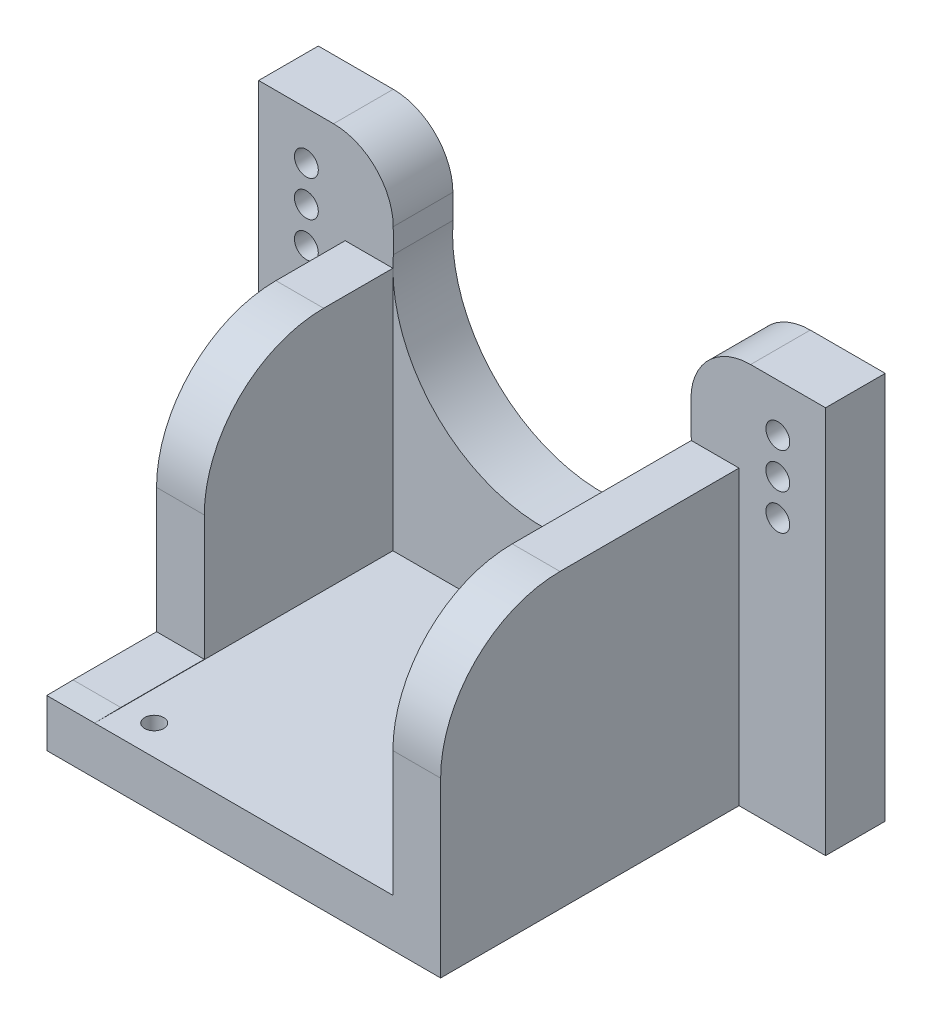
SolidWorks part; units mm, degrees
ref_plane "Front Plane" through (0, 0, 0) normal (0, 0, 1) x (1, 0, 0)
ref_plane "Top Plane" through (0, 0, 0) normal (0, 1, 0) x (1, 0, 0)
ref_plane "Right Plane" through (0, 0, 0) normal (1, 0, 0) x (0, 0, -1)
sketch "Sketch1" plane through (0, 0, 0) normal (0, 0, 1) x (1, 0, 0)
  line L0 (-25, 20.9224) -> (-66.8811, 20.9224) construction
  line L1 (-25, 12.9224) -> (-25, -3.0776) construction
  line L2 (25, 12.9224) -> (25, -3.0776) construction
  line L3 (-25, 4.9224) -> (25, 4.9224) construction
  line L4 (61.331, -36.0776) -> (47.5, -36.0776) construction
  line L5 (-39.5, 14.9224) -> (-39.5, -45.2177) construction
  line L6 (39.5, 12.9224) -> (39.5, -45.2177) construction
  line L7 (61.331, 12.9224) -> (24.9542, 12.9224) construction
  line L8 (61.331, 6.9224) -> (24.9199, 6.9224) construction
  line L9 (61.331, 0.9224) -> (-66.8811, 0.9224) construction
  line L10 (-47.5, 14.9224) -> (-47.5, -36.0776) construction
  line L11 (-47.5, -36.0776) -> (-47.5, 20.9224)
  line L12 (0, 6.9224) -> (0, -45.2177) construction
  line L13 (-47.5, 20.9224) -> (-25, 20.9224)
  line L14 (-25, 20.9224) -> (-24.9199, 6.9224)
  line L16 (-24.9542, 12.9224) -> (-66.8811, 12.9224) construction
  line L17 (61.331, 12.9224) -> (-66.8811, 12.9224) construction
  line L18 (-24.9199, 6.9224) -> (-66.8811, 6.9224) construction
  line L19 (61.331, 6.9224) -> (-66.8811, 6.9224) construction
  line L20 (61.331, 20.9224) -> (-66.8811, 20.9224) construction
  line L21 (-33, -44.0776) -> (-33, -36.0776)
  line L22 (-33, 12.9224) -> (-33, -3.0776) construction
  line L23 (-33, -44.0776) -> (33, -44.0776)
  line L24 (-17.0457, 28.9224) -> (-16.92, 6.9682) construction
  line L25 (-55.5, 28.9224) -> (-17.0457, 28.9224) construction
  line L26 (-55.5, -44.0776) -> (-55.5, 28.9224) construction
  line L27 (-55.5, -44.0776) -> (0, -44.0776) construction
  line L28 (-25, -36.0776) -> (-25, 4.9224)
  line L29 (-47.5, 14.9224) -> (-47.5, -45.2177) construction
  line L30 (-25, 4.9224) -> (-33, 4.9224)
  line L31 (-33, 4.9224) -> (-33, -36.0776)
  line L32 (25, 4.9224) -> (33, 4.9224)
  line L33 (33, 4.9224) -> (33, -36.0776)
  line L34 (25, -36.0776) -> (25, 4.9224)
  line L35 (33, -44.0776) -> (33, -36.0776)
  line L36 (-33, -36.0776) -> (0, -36.0776)
  line L37 (47.5, -36.0776) -> (47.5, 20.9224)
  line L38 (47.5, 20.9224) -> (25, 20.9224)
  line L39 (25, 20.9224) -> (24.9199, 6.9224)
  line L40 (-25, -36.0776) -> (25, -36.0776)
  line L41 (-47.5, -36.0776) -> (-47.5, -44.0776)
  line L42 (-47.5, -44.0776) -> (-33, -44.0776)
  line L43 (47.5, -36.0776) -> (47.5, -44.0776)
  line L44 (47.5, -44.0776) -> (33, -44.0776)
  line L45 (33, -36.0776) -> (-33, -36.0776) construction
  line L46 (61.331, -36.0776) -> (-66.8811, -36.0776) construction
  line L47 (33, -36.0776) -> (0, -36.0776)
  line L48 (-47.5, -36.0776) -> (0, -36.0776) construction
  line L49 (-47.5, -36.0776) -> (-66.8811, -36.0776) construction
  circle A0 centre (-39.5, 12.9224) radius 2
  circle A1 centre (-39.5, 6.9224) radius 2
  circle A2 centre (-39.5, 0.9224) radius 2
  arc A3 (-24.9199, 6.9224) -> (24.9199, 6.9224) centre (0, 4.9224) ccw
  arc A4 (24.6779, 0.9224) -> (24.9199, 6.9224) centre (0, 4.9224) ccw
  circle A5 centre (39.5, 0.9224) radius 2
  circle A6 centre (39.5, 12.9224) radius 2
  circle A7 centre (39.5, 6.9224) radius 2
  dimension "D7" = 6
  dimension "D9" = 4
  dimension "D10" = 4
  dimension "D11" = 4
  dimension "D3" = 41
  dimension "D12" = 8
  dimension "D5" = 8
  dimension "D2" = 20
  dimension "D4" = 8
  dimension "D6" = 49
  dimension "D8" = 6
extrude "Boss-Extrude2" add sketch "Sketch1" along normal blind 10 contours A3 L14 L13 L11 L41 L42 L21 L31 L30 A0 A1 A2 | A3 L28 L36 L40 L34 | A3 L32 L33 L35 L44 L43 L37 L38 L39 A6 A5 A7 region at (-38.8748, -9.2044, 0) region at (38.8748, -9.2044, 0) region at (0, -24.6664, 0)
extrude "Boss-Extrude3" add sketch "Sketch1<8>" along normal blind 60 contours L31 L36 L28 L30 | L35 L47 L40 L36 L21 L23 | L47 L33 L32 L34 region at (0, -40.0776, 0) region at (-29, -15.5776, 0) region at (29, -15.5776, 0)
sketch "Sketch1<8>" plane through (0, 0, 0) normal (0, 0, 1) x (1, 0, 0) same geometry as "Sketch1"
sketch "Sketch2" plane through (-33, 0, 0) normal (-1, 0, 0) x (0, 0, 1)
  line L0 (35, 4.9224) -> (35, -44.0776) construction
  line L1 (60, 4.9224) -> (10, 4.9224) construction
  line L2 (60, -44.0776) -> (10, -44.0776) construction
  line L4 (48.6, 4.9224) -> (48.6, -44.0776) construction
  line L5 (60, -36.0776) -> (10, -36.0776)
  line L6 (60, -36.0776) -> (10, -36.0776) construction
  line L7 (60, -29.1776) -> (10, -29.1776) construction
  line L8 (41.6062, -22.3299) -> (41.6062, 4.9224)
  line L9 (41.6062, -22.3299) -> (41.6062, -36.0252)
  line L10 (41.6062, 4.9224) -> (60, 4.9224)
  line L11 (41.6062, -36.0252) -> (55.5938, -36.0252)
  line L12 (41.6062, -22.3299) -> (55.5938, -36.0252) construction
  line L13 (55.5938, -22.3299) -> (41.6062, -36.0252) construction
  line L14 (60, 4.9224) -> (60, -36.0776)
  line L15 (60, -36.0776) -> (55.5938, -36.0252)
  point P13 (48.6, -29.1776)
  dimension "D1" = 8
  dimension "D2" = 13.6
  dimension "D3" = 6.9
extrude "Cut-Extrude1" cut sketch "Sketch2" against normal up to next
fillet "Fillet3" radius 20 1 edges at (29, 4.9224, 60)
fillet "Fillet4" radius 10 2 edges at (25, 20.9224, 5) (-25, 20.9224, 5)
sketch "Sketch3" plane through (0, -36.0776, 0) normal (0, 1, 0) x (1, 0, 0)
  line L8 (20, -55) -> (20, -15)
  line L9 (20, -15) -> (-20, -15)
  line L10 (-20, -15) -> (-20, -55)
  line L11 (-20, -55) -> (20, -55)
  line L12 (20, -55) -> (20, -15) construction
  line L13 (20, -15) -> (-20, -15) construction
  line L14 (-20, -15) -> (-20, -55) construction
  line L15 (-20, -55) -> (20, -55) construction
  circle A0 centre (-20, -55) radius 1.6
  circle A1 centre (20, -15) radius 1.6
  dimension "D1" = 5
fillet "Fillet5" radius 20 1 edges at (-29, 4.9224, 41.6062)
extrude "Cut-Extrude3" cut sketch "Sketch3" against normal through all
